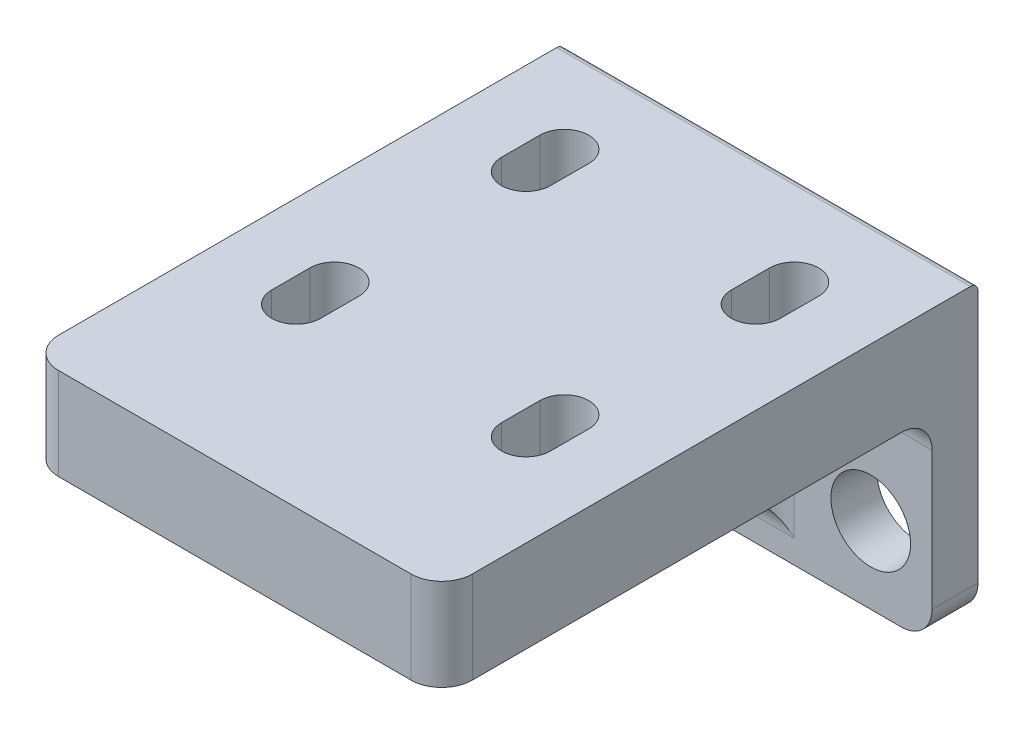
SolidWorks part; units mm, degrees
ref_plane "前视基准面" through (0, 0, 0) normal (0, 0, 1) x (1, 0, 0)
ref_plane "上视基准面" through (0, 0, 0) normal (0, 1, 0) x (1, 0, 0)
ref_plane "右视基准面" through (0, 0, 0) normal (1, 0, 0) x (0, 0, -1)
sketch "草图1" plane through (0, 0, 0) normal (0, 0, 1) x (1, 0, 0)
  line L1 (0, 0) -> (27, 0)
  line L2 (0, 0) -> (0, -16)
  line L3 (0, -16) -> (27, -16)
  line L4 (27, 0) -> (27, -16)
  dimension "D1" = 16
  dimension "D2" = 2
  dimension "D3" = 27
extrude "凸台-拉伸2" add sketch "草图1" along normal blind 2 and the other way blind 1 contours L2 L1 L4 L3
sketch "草图3" plane through (0, 0, 0) normal (0, 1, 0) x (1, 0, 0)
  line L0 (27, -2) -> (27, 1) construction
  line L1 (0, 0) -> (27, 0)
  line L2 (0, 0) -> (0, -34)
  line L3 (0, -34) -> (27, -34)
  line L4 (27, 0) -> (27, -34)
  dimension "D1" = 34
extrude "凸台-拉伸4" add sketch "草图3" against normal blind 3 and the other way blind 3
sketch "草图4" plane through (0, -3, 0) normal (0, -1, 0) x (-1, 0, 0)
  line L0 (-6, -7.5) -> (-6, -5) construction
  line L1 (-7.6, -7.5) -> (-7.6, -5)
  line L2 (-4.4, -7.5) -> (-4.4, -5)
  line L3 (-21, -7.5) -> (-21, -5) construction
  line L4 (-22.6, -7.5) -> (-22.6, -5)
  line L5 (-19.4, -7.5) -> (-19.4, -5)
  line L6 (-6, -22.5) -> (-6, -20) construction
  line L7 (-7.6, -22.5) -> (-7.6, -20)
  line L8 (-4.4, -22.5) -> (-4.4, -20)
  line L9 (-21, -22.5) -> (-21, -20) construction
  line L10 (-22.6, -22.5) -> (-22.6, -20)
  line L11 (-19.4, -22.5) -> (-19.4, -20)
  line L12 (0, -2) -> (0, -34) construction
  line L13 (-27, -34) -> (-27, -2) construction
  line L14 (0, -2) -> (-27, -2) construction
  arc A0 (-7.6, -7.5) -> (-4.4, -7.5) centre (-6, -7.5) ccw
  arc A1 (-4.4, -5) -> (-7.6, -5) centre (-6, -5) ccw
  arc A2 (-22.6, -7.5) -> (-19.4, -7.5) centre (-21, -7.5) ccw
  arc A3 (-19.4, -5) -> (-22.6, -5) centre (-21, -5) ccw
  arc A4 (-7.6, -22.5) -> (-4.4, -22.5) centre (-6, -22.5) ccw
  arc A5 (-4.4, -20) -> (-7.6, -20) centre (-6, -20) ccw
  arc A6 (-22.6, -22.5) -> (-19.4, -22.5) centre (-21, -22.5) ccw
  arc A7 (-19.4, -20) -> (-22.6, -20) centre (-21, -20) ccw
  point P2 (-6, -6.25)
  point P11 (-21, -6.25)
  point P18 (-6, -21.25)
  point P25 (-21, -21.25)
  dimension "D1" = 2
  dimension "D6" = 1.6
  dimension "D7" = 3
  dimension "D3" = 32
  dimension "D4" = 4.4
  dimension "D5" = 11.8
  dimension "D8" = 2.5
  dimension "D2" = 2
extrude "切除-拉伸11" cut sketch "草图4" against normal blind 13
sketch "草图8" plane through (0, -3, 0) normal (0, -1, 0) x (-1, 0, 0)
  line L0 (0, -34) -> (-27, -34) construction
  point P0 (-13.5, -34)
sketch "草图9" plane through (0, 0, 2) normal (0, 0, 1) x (1, 0, 0)
  line L0 (0, -16) -> (27, -16) construction
  point P0 (13.5, -16)
sketch "草图12" plane through (0, 0, 2) normal (0, 0, 1) x (1, 0, 0)
  point P0 (13.5, -3)
ref_plane "基准面4" through (13.5, 0, 0) normal (-1, 0, 0) x (0, 0, 1)
sketch "草图13" plane through (13.5, 0, 0) normal (-1, 0, 0) x (0, 0, 1)
  line L0 (2, -13) -> (34, -3)
  line L2 (2, -13) -> (2, -3)
  line L3 (2, -3) -> (34, -3)
extrude "凸台-拉伸5" add sketch "草图13" against normal blind 2.5 and the other way blind 2.5
fillet "圆角2" radius 2 6 edges at (5.5, -3, 2) (21.5, -3, 2) (0, -16, 0.5) (27, -16, 0.5) (27, 0, 34) (0, 0, 34)
fillet "圆角3" radius 2 7 edges at (13.5, -13, 2) (16, -3, 19) (16, -3.5858, 2.5858) (16, -9, 2) (11, -9, 2) (11, -3, 19) (11, -3.5858, 2.5858)
sketch "草图14" plane through (0, 0, 0) normal (0, 0, -1) x (-1, 0, 0)
  line L1 (-27, 3) -> (0, 3)
  line L2 (-27, 3) -> (-27, 0)
  line L3 (-27, 0) -> (0, 0)
  line L4 (0, 3) -> (0, 0)
extrude "凸台-拉伸6" add sketch "草图14" along normal blind 1
fillet "圆角5" radius 0.5 1 edges at (13.5, 3, -1)
sketch "草图16" plane through (0, 0, 2) normal (0, 0, 1) x (1, 0, 0)
  line L0 (0, -5) -> (0, -14) construction
  line L1 (9, -5) -> (7.249, -5) construction
  line L2 (27, -5) -> (27, -14) construction
  line L3 (27, -5) -> (22.249, -5) construction
  circle A0 centre (4, -11) radius 2.6
  circle A3 centre (23, -11) radius 2.6
  dimension "D1" = 4
  dimension "D2" = 6
  dimension "D5" = 4
  dimension "D8" = 6
extrude "切除-拉伸12" cut sketch "草图16" against normal blind 4
